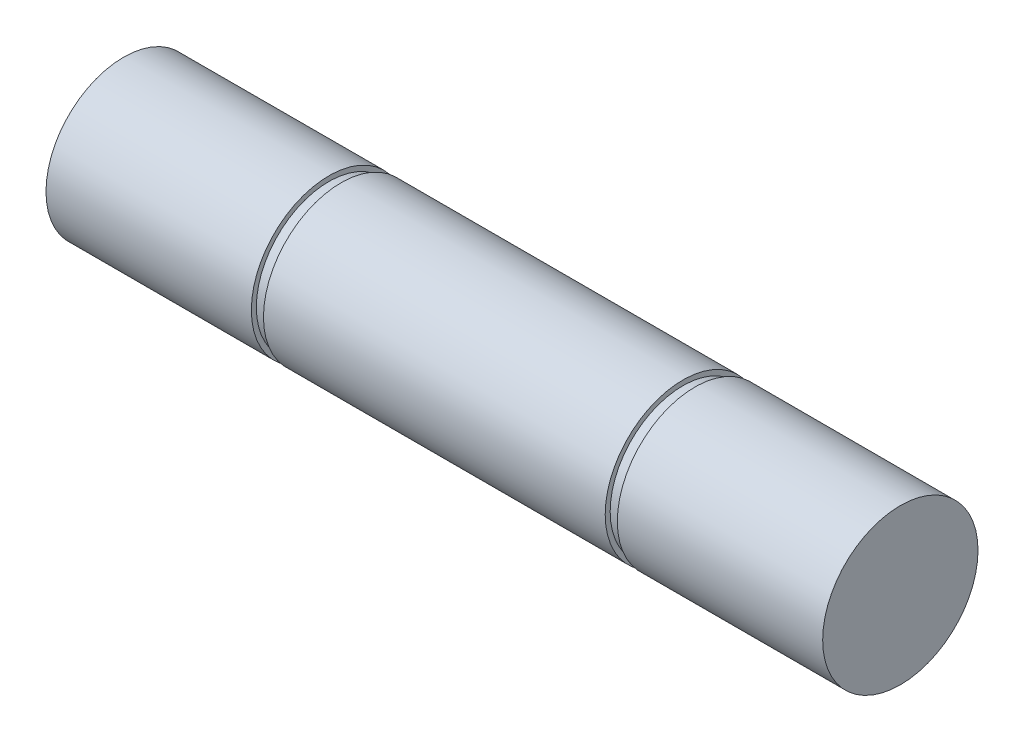
SolidWorks part; units mm, degrees
material "6061 Alloy"
ref_plane "Front Plane" through (0, 0, 0) normal (0, 0, 1) x (1, 0, 0)
ref_plane "Top Plane" through (0, 0, 0) normal (0, 1, 0) x (1, 0, 0)
ref_plane "Right Plane" through (0, 0, 0) normal (1, 0, 0) x (0, 0, -1)
sketch "Sketch1" plane through (0, 0, 0) normal (1, 0, 0) x (0, 0, -1)
  circle A0 centre (0, 0) radius 6.35
  dimension "D1" = 12.7
extrude "Boss-Extrude1" add sketch "Sketch1" along normal blind 63.5
ref_plane "Plane2" through (31.75, 0, 0) normal (-1, 0, 0) x (0, 0, 1)
ref_plane "Plane1" through (17.78, 0, 0) normal (-1, 0, 0) x (0, 0, 1)
sketch "Sketch2" plane through (17.78, 0, 0) normal (-1, 0, 0) x (0, 0, 1)
  circle A0 centre (0, 0) radius 5.9436
  circle A1 centre (0, 0) radius 6.35
  circle A2 centre (0, 0) radius 6.35 construction
  dimension "D1" = 11.8872
extrude "Cut-Extrude1" cut sketch "Sketch2" along normal blind 0.9906
mirror "Mirror1" about plane through (31.75, 0, 0) normal (-1, 0, 0) of "Cut-Extrude1"
